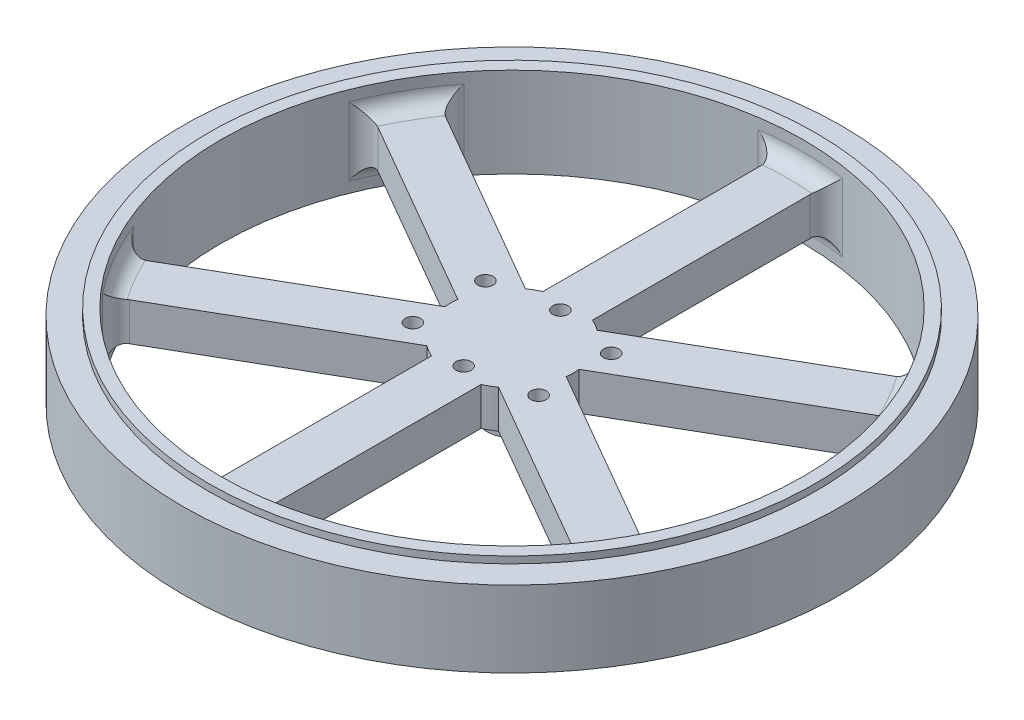
SolidWorks part; units mm, degrees
ref_plane "Front Plane" through (0, 0, 0) normal (0, 0, 1) x (1, 0, 0)
ref_plane "Top Plane" through (0, 0, 0) normal (0, 1, 0) x (1, 0, 0)
ref_plane "Right Plane" through (0, 0, 0) normal (1, 0, 0) x (0, 0, -1)
sketch "Sketch1" plane through (0, 0, 0) normal (0, 1, 0) x (1, 0, 0)
  circle A0 centre (0, 0) radius 43.25
  dimension "D1" = 86.5
extrude "Boss-Extrude1" add sketch "Sketch1" along normal blind 10
sketch "Sketch3" plane through (0, 10, 0) normal (0, 1, 0) x (1, 0, 0)
  circle A0 centre (0, 0) radius 38.25
  circle A1 centre (0, 0) radius 43.25 construction
  circle A2 centre (0, 0) radius 39.85
  dimension "D1" = 5
  dimension "D2" = 1.6
extrude "Boss-Extrude2" add sketch "Sketch3" along normal blind 0.9
ref_plane "Plane1" through (0, 5, 0) normal (0, 1, 0) x (1, 0, 0)
mirror "Mirror1" about plane through (0, 5, 0) normal (0, 1, 0) of "Boss-Extrude2"
sketch "Sketch4" plane through (0, 10, 0) normal (0, 1, 0) x (1, 0, 0)
  circle A0 centre (0, 0) radius 38.25
  circle A1 centre (0, 0) radius 38.25 construction
extrude "Cut-Extrude1" cut sketch "Sketch4" against normal through all
sketch "Sketch5" plane through (0, 5, 0) normal (0, 1, 0) x (1, 0, 0)
  line L0 (0, 8) -> (0, 38.25) construction
  line L1 (3.25, 7.3101) -> (3.25, 38.1117)
  line L2 (-3.25, 7.3101) -> (-3.25, 38.1117)
  line L3 (7.9557, 0.8405) -> (34.6307, 16.2413)
  line L4 (4.7057, 6.4696) -> (31.3807, 21.8704)
  line L5 (4.7057, -6.4696) -> (31.3807, -21.8704)
  line L6 (7.9557, -0.8405) -> (34.6307, -16.2413)
  line L7 (-3.25, -7.3101) -> (-3.25, -38.1117)
  line L8 (3.25, -7.3101) -> (3.25, -38.1117)
  line L9 (-7.9557, -0.8405) -> (-34.6307, -16.2413)
  line L10 (-4.7057, -6.4696) -> (-31.3807, -21.8704)
  line L11 (-4.7057, 6.4696) -> (-31.3807, 21.8704)
  line L12 (-7.9557, 0.8405) -> (-34.6307, 16.2413)
  circle A0 centre (0, 0) radius 8
  circle A1 centre (0, 0) radius 38.25 construction
  circle A3 centre (0, 0) radius 38.25
  point P34 (0, 0)
  dimension "D1" = 16
  dimension "D2" = 3.25
  dimension "D3" = 6
extrude "Boss-Extrude3" add sketch "Sketch5" along normal blind 2.5 and the other way blind 2.5 contours L11 A3 L12 A0 | L0 A0 L1 A3 | A0 L0 A3 L2 | L3 A3 L4 A0 | L5 A3 L6 A0 | L7 A3 L8 A0 | L9 A3 L10 A0 | A0 region at (-1.6299, 5, -22.9884) region at (1.6299, 5, -22.9884) region at (0, 5, 0) region at (19.9085, 5, -11.4942) region at (-19.9085, 5, -11.4942) region at (-19.9085, 5, 11.4942) region at (19.9085, 5, 11.4942) region at (0, 5, 22.9884)
sketch "Sketch6" plane through (0, 2.5, 0) normal (0, -1, 0) x (-1, 0, 0)
  circle A0 centre (0, 0) radius 3.3
  dimension "D1" = 6.6
extrude "Boss-Extrude4" add sketch "Sketch6" along normal blind 4
sketch "Sketch7" plane through (0, 2.5, 0) normal (0, -1, 0) x (-1, 0, 0)
  line L0 (0, -3.3) -> (0, -38.25) construction
  line L1 (-3.3, 0) -> (-38.25, 0) construction
  line L2 (0, 0) -> (-33.1255, -19.125) construction
  line L3 (-7.9557, -0.8405) -> (-34.6307, -16.2413) construction
  circle A0 centre (0, 0) radius 3.3 construction
  arc A1 (-3.25, -38.1117) -> (3.25, -38.1117) centre (0, 0) ccw construction
  circle A2 centre (0, -6.35) radius 1
  circle A3 centre (0, 0) radius 38.25 construction
  circle A4 centre (0, 0) radius 38.25 construction
  circle A5 centre (0, 6.35) radius 1
  circle A6 centre (-8.2498, -4.763) radius 1
  circle A7 centre (-8.2498, 4.763) radius 1
  circle A9 centre (8.2498, 4.763) radius 1
  circle A10 centre (8.2498, -4.763) radius 1
  circle A12 centre (0, -9.526) radius 1 [skipped]
  circle A13 centre (0, 9.526) radius 1 [skipped]
  point P34 (0, 0)
  dimension "D2" = 2
  dimension "D3" = 2
  dimension "D1" = 6.35
  dimension "D4" = 9.526
  dimension "D5" = 6
extrude "Cut-Extrude2" cut sketch "Sketch7" against normal through all
fillet "Fillet1" radius 2 24 edges at (33.1255, 7.5, 19.125) (33.1255, 2.5, 19.125) (34.6307, 5, 16.2413) (31.3807, 5, 21.8704) (0, 2.5, -38.25) (-33.1255, 2.5, -19.125) (-33.1255, 2.5, 19.125) (0, 2.5, 38.25) (-3.25, 5, 38.1117) (-3.25, 5, -38.1117) (-34.6307, 5, 16.2413) (3.25, 5, 38.1117) (-34.6307, 5, -16.2413) (3.25, 5, -38.1117) (-31.3807, 5, 21.8704) (-31.3807, 5, -21.8704) (0, 7.5, 38.25) (-33.1255, 7.5, 19.125) (-33.1255, 7.5, -19.125) (0, 7.5, -38.25) (33.1255, 7.5, -19.125) (34.6307, 5, -16.2413) (33.1255, 2.5, -19.125) (31.3807, 5, -21.8704)
ref_point "Point1"
ref_axis "Axis1" through (0, 0, 0) along (0, -1, 0)
